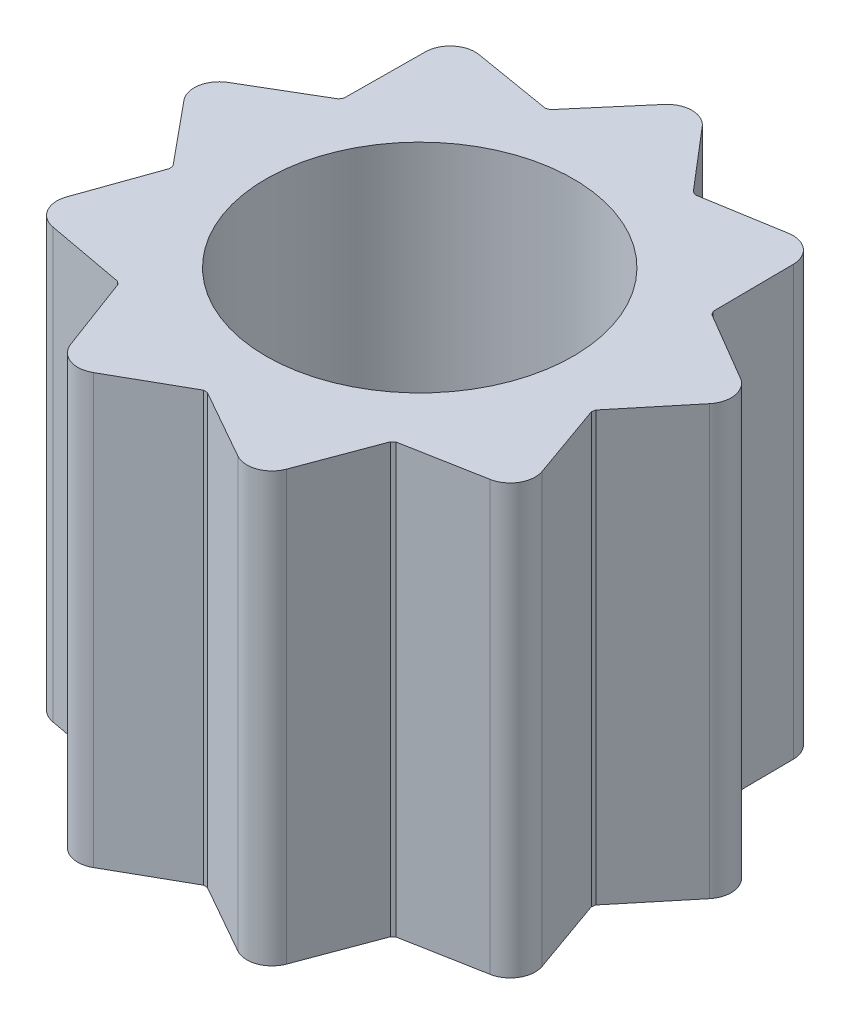
SolidWorks part; units mm, degrees
ref_plane "Front Plane" through (0, 0, 0) normal (0, 0, 1) x (1, 0, 0)
ref_plane "Top Plane" through (0, 0, 0) normal (0, 1, 0) x (1, 0, 0)
ref_plane "Right Plane" through (0, 0, 0) normal (1, 0, 0) x (0, 0, -1)
sketch "Sketch1" plane through (0, 0, 0) normal (0, 1, 0) x (1, 0, 0)
  line L0 (0, 3) -> (0, 4) construction
  line L1 (0, 4) -> (1, 2.8284)
  line L2 (0, 4) -> (-1, 2.8284)
  line L3 (2.5712, 3.0642) -> (1.052, 2.8095)
  line L4 (2.5712, 3.0642) -> (2.5841, 1.5239)
  line L5 (3.9392, 0.6946) -> (2.6118, 1.476)
  line L6 (3.9392, 0.6946) -> (2.9591, -0.4937)
  line L7 (3.4641, -2) -> (2.9495, -0.5482)
  line L8 (3.4641, -2) -> (1.9495, -2.2802)
  line L9 (1.3681, -3.7588) -> (1.9071, -2.3158)
  line L10 (1.3681, -3.7588) -> (0.0277, -2.9999)
  line L11 (-1.3681, -3.7588) -> (-0.0277, -2.9999)
  line L12 (-1.3681, -3.7588) -> (-1.9071, -2.3158)
  line L13 (-3.4641, -2) -> (-1.9495, -2.2802)
  line L14 (-3.4641, -2) -> (-2.9495, -0.5482)
  line L15 (-3.9392, 0.6946) -> (-2.9591, -0.4937)
  line L16 (-3.9392, 0.6946) -> (-2.6118, 1.476)
  line L17 (-2.5712, 3.0642) -> (-2.5841, 1.5239)
  line L18 (-2.5712, 3.0642) -> (-1.052, 2.8095)
  circle A0 centre (0, 0) radius 4 construction
  circle A1 centre (0, 0) radius 3
  circle A3 centre (0, 0) radius 2.15
  point P26 (0, 0)
  dimension "D1" = 8
  dimension "D4" = 2
  dimension "D6" = 4.3
  dimension "D3" = 1
  dimension "D5" = 9
extrude "Boss-Extrude1" add sketch "Sketch1" along normal blind 6 contours A1 L1 L2 | A1 L4 L3 | A1 L6 L5 | A1 L8 L7 | A1 L10 L9 | A1 L12 L11 | A1 A3 | A1 L14 L13 | A1 L16 L15 | A1 L18 L17 region at (0, 0, -3.2976) region at (0.997, 0, -2.7393) region at (2.1196, 0, -2.5261) region at (-2.1196, 0, -2.5261) region at (3.2475, 0, -0.5726) region at (-3.2475, 0, -0.5726) region at (-2.8558, 0, 1.6488) region at (2.8558, 0, 1.6488) region at (-1.1278, 0, 3.0987) region at (1.1278, 0, 3.0987)
fillet "Fillet1" radius 0.35 9 edges at (2.5712, 3, -3.0642) (3.9392, 3, -0.6946) (3.4641, 3, 2) (0, 3, -4) (-1.3681, 3, 3.7588) (1.3681, 3, 3.7588) (-2.5712, 3, -3.0642) (-3.4641, 3, 2) (-3.9392, 3, -0.6946)
